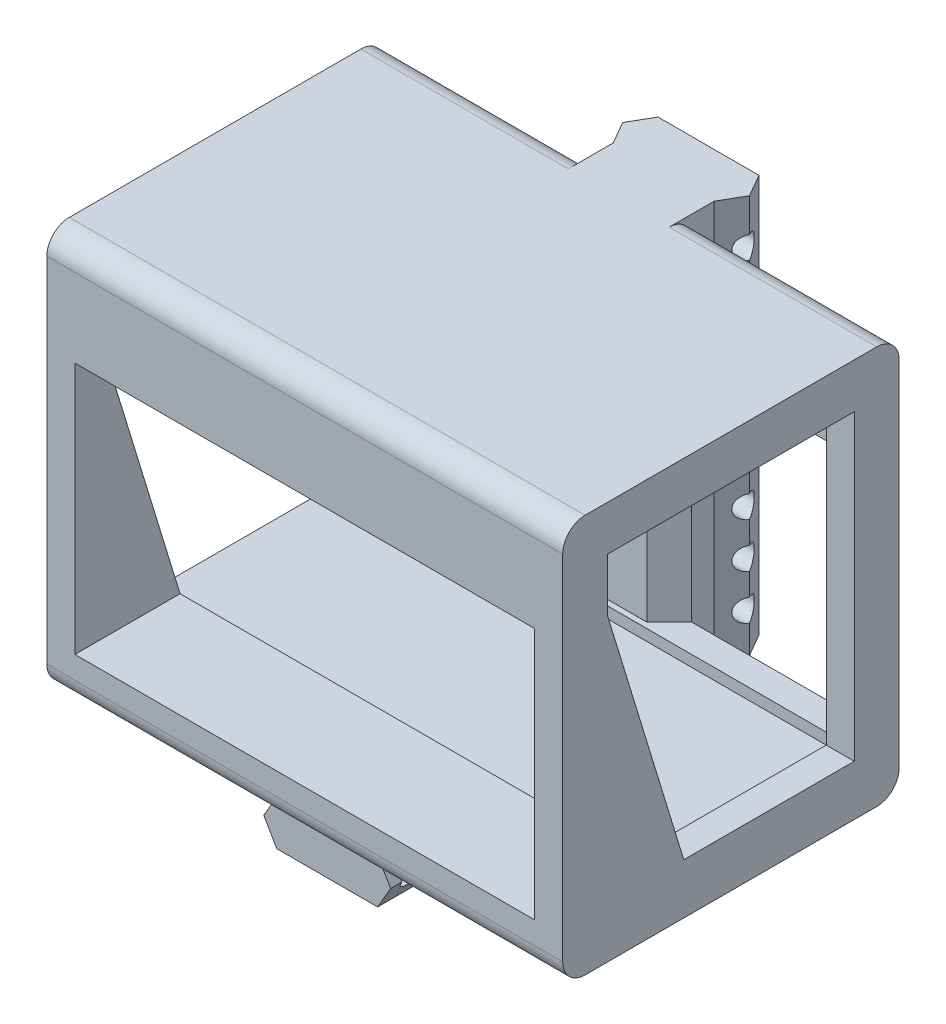
SolidWorks part; units mm, degrees
ref_plane "Front Plane" through (0, 0, 0) normal (0, 0, 1) x (1, 0, 0)
ref_plane "Top Plane" through (0, 0, 0) normal (0, 1, 0) x (1, 0, 0)
ref_plane "Right Plane" through (0, 0, 0) normal (1, 0, 0) x (0, 0, -1)
sketch "Sketch4" plane through (0, 0, 0) normal (1, 0, 0) x (0, 0, -1)
  line L1 (-30, 32.5) -> (30, 32.5)
  line L2 (-30, 32.5) -> (-30, -38.5)
  line L3 (-30, -38.5) -> (30, -38.5)
  line L4 (30, 32.5) -> (30, -38.5)
  dimension "D1" = 60
  dimension "D2" = 71
  dimension "D3" = 32.5
  dimension "D4" = 30
sketch "Sketch5" plane through (0, 0, 0) normal (1, 0, 0) x (0, 0, -1)
  line L0 (-25, 27.5) -> (-25, 14.5)
  line L1 (-25, 14.5) -> (-10.6307, -32.5)
  line L2 (-10.6307, -32.5) -> (25, -32.5)
  line L3 (25, -32.5) -> (25, 27.5)
  line L4 (25, 27.5) -> (-25, 27.5)
  line L5 (-30, 32.5) -> (-30, -38.5) construction
  line L6 (30, 32.5) -> (30, -38.5) construction
  line L7 (-30, 32.5) -> (30, 32.5) construction
  dimension "D1" = 107
  dimension "D2" = 13
  dimension "D3" = 60
  dimension "D4" = 50
  dimension "D5" = 25
  dimension "D6" = 27.5
  dimension "D7" = 5
  dimension "D8" = 5
  dimension "D9" = 5
extrude "Base" add sketch "Sketch4" along normal blind 46 and the other way blind 46
extrude "LIDAR" cut sketch "Sketch5" against normal up to surface (46 mm away) and the other way blind 41 up to face at (-46, -3, 0)
sketch "Sketch6" plane through (0, 0, 0) normal (0, 0, 1) x (1, 0, 0)
  line L0 (-46, 32.5) -> (-46, -38.5) construction
  line L1 (-41, 14.5) -> (41, 14.5)
  line L2 (-41, 14.5) -> (-41, -30.5)
  line L3 (-41, -30.5) -> (41, -30.5)
  line L4 (41, 14.5) -> (41, -30.5)
  line L5 (46, 32.5) -> (46, -38.5) construction
  line L6 (-46, 32.5) -> (46, 32.5) construction
  line L7 (-46, -38.5) -> (46, -38.5) construction
  dimension "D1" = 5
  dimension "D2" = 5
  dimension "D3" = 18
  dimension "D4" = 8
extrude "HoleFrontBack" cut sketch "Sketch6" against normal through all both and the other way through all
fillet "Fillet2" radius 4 4 edges at (0, 32.5, -30) (0, -38.5, -30) (0, -38.5, 30) (0, 32.5, 30)
sketch "Sketch9" plane through (0, 0, 0) normal (0, 1, 0) x (1, 0, 0)
  line L0 (-46, 26) -> (-46, -26) construction
  line L1 (46, 26) -> (-46, 26) construction
  circle A0 centre (-42.9, 22.29) radius 1
  dimension "D1" = 2
  dimension "D2" = 3.1
  dimension "D3" = 3.71
sketch "Sketch11" plane through (0, 0, -30) normal (0, 0, -1) x (-1, 0, 0)
  line L1 (-9, 32.5) -> (9, 32.5)
  line L2 (-9, 32.5) -> (-9, -38.5)
  line L3 (-9, -38.5) -> (9, -38.5)
  line L4 (9, 32.5) -> (9, -38.5)
  line L6 (0, 32.5) -> (0, -38.5) construction
  line L11 (-46, 32.5) -> (46, 32.5) construction
  line L12 (46, -38.5) -> (-46, -38.5) construction
  point P4 (0, 0)
  dimension "D1" = 18
extrude "Boss-Extrude1" add sketch "Sketch11" along normal blind 4 and the other way up to vertex (4 mm away) other way up to point (46, 32.5, -26)
sketch "Sketch12" plane through (0, 32.5, 0) normal (0, 1, 0) x (1, 0, 0)
  line L0 (-9, 34) -> (-11.3094, 38)
  line L1 (-11.3094, 38) -> (-9, 42)
  line L2 (-9, 42) -> (9, 42)
  line L3 (9, 42) -> (11.3094, 38)
  line L4 (11.3094, 38) -> (9, 34)
  line L5 (9, 26) -> (9, 34) construction
  line L6 (-9, 34) -> (9, 34) construction
  line L7 (9, 34) -> (-9, 34)
  dimension "D1" = 8
  dimension "D2" = 120
  dimension "D3" = 120
  dimension "D4" = 120
sketch "Sketch13" plane through (0, 0, -34) normal (0, 0, -1) x (-1, 0, 0)
  line L0 (-9, -38.5) -> (9, -38.5)
  line L1 (9, -38.5) -> (11.3094, -42.5)
  line L2 (11.3094, -42.5) -> (9, -46.5)
  line L3 (9, -46.5) -> (-9, -46.5)
  line L4 (-9, -46.5) -> (-11.3094, -42.5)
  line L5 (-11.3094, -42.5) -> (-9, -38.5)
  dimension "D1" = 120
  dimension "D2" = 120
  dimension "D3" = 120
  dimension "D4" = 8
extrude "Boss-Extrude3" add sketch "Sketch13" against normal up to vertex (60 mm away) up to point (46, -38.5, 26)
extrude "Boss-Extrude4" add sketch "Sketch12" against normal up to vertex (71 mm away) up to point (9, -38.5, -34)
sketch "Sketch14" plane through (46, 0, 0) normal (1, 0, 0) x (0, 0, -1)
  line L0 (38, -38.5) -> (38, 32.5) construction
  line L1 (38, 24.5) -> (38, 16.5) construction
  line L2 (-26, -42.5) -> (34, -42.5) construction
  line L3 (34, -42.5) -> (34, -46.5) construction
  line L4 (26, -42.5) -> (18, -42.5) construction
  circle A0 centre (38, 24.5) radius 2
  circle A1 centre (38, 16.5) radius 2
  circle A2 centre (38, 8.5) radius 2
  circle A3 centre (38, 0.5) radius 2
  circle A4 centre (38, -7.5) radius 2
  circle A5 centre (38, -15.5) radius 2
  circle A6 centre (38, -23.5) radius 2
  circle A7 centre (38, -31.5) radius 2
  circle A8 centre (26, -42.5) radius 2
  circle A9 centre (18, -42.5) radius 2
  circle A10 centre (10, -42.5) radius 2
  circle A11 centre (2, -42.5) radius 2
  circle A12 centre (-6, -42.5) radius 2
  circle A13 centre (-14, -42.5) radius 2
  circle A14 centre (-22, -42.5) radius 2
  dimension "D1" = 4
  dimension "D5" = 4
  dimension "D2" = 8
  dimension "D4" = 8
  dimension "D6" = 8
  dimension "D8" = 8
  dimension "D3" = 8
  dimension "D7" = 7
extrude "Cut-Extrude1" cut sketch "Sketch14" against normal up to vertex (57.3094 mm away) up to point (-11.3094, -42.5, 26)
sketch "Sketch15" plane through (46, 0, 0) normal (1, 0, 0) x (0, 0, -1)
  line L0 (-22, 14.9484) -> (-8.4108, -29.5)
  line L1 (-8.4108, -29.5) -> (22, -29.5)
  line L2 (22, -29.5) -> (22, 14.6412)
  line L3 (22, 14.6412) -> (22, 24.5)
  line L4 (22, 24.5) -> (-22, 24.5)
  line L5 (-22, 24.5) -> (-22, 14.9484)
  line L6 (-11.2421, -30.5) -> (-25, 14.5) construction
  line L7 (-25, 27.5) -> (-25, 14.5) construction
  line L8 (25, 27.5) -> (-25, 27.5) construction
  line L9 (25, 14.5) -> (25, 27.5) construction
  line L10 (-10.6307, -32.5) -> (25, -32.5) construction
  dimension "D1" = 3
  dimension "D2" = 3
  dimension "D3" = 3
  dimension "D4" = 3
  dimension "D5" = 3
extrude "Cut-Extrude2" cut sketch "Sketch15" against normal up to surface (5 mm away) up to face at (41, -6.1667, -2.3439)
chamfer "Chamfer1" distance 4 angle 45 2 edges at (9, -8, -26) (-9, -8, -26)
